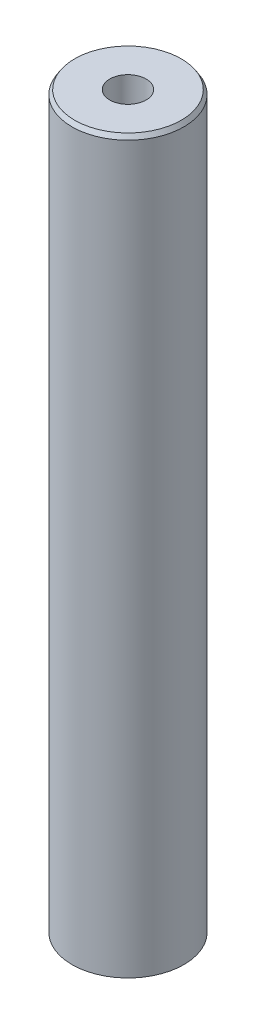
SolidWorks part; units mm, degrees
ref_plane "Front Plane" through (0, 0, 0) normal (0, 0, 1) x (1, 0, 0)
ref_plane "Top Plane" through (0, 0, 0) normal (0, 1, 0) x (1, 0, 0)
ref_plane "Right Plane" through (0, 0, 0) normal (1, 0, 0) x (0, 0, -1)
sketch "Sketch1" plane through (0, 0, 0) normal (0, 1, 0) x (1, 0, 0)
  circle A0 centre (0, 0) radius 35
  dimension "SHAFT_OD" = 70
extrude "Boss-Extrude1" add sketch "Sketch1" along normal blind 457.9796
sketch "Sketch2" plane through (0, 0, 0) normal (0, 1, 0) x (1, 0, 0)
  circle A0 centre (0, 0) radius 11.3816
  dimension "BORE_D" = 22.7633
extrude "Cut-Extrude1" cut sketch "Sketch2" along normal through all
chamfer "Chamfer1" distance 2.7229 angle 31.839 2 edges at (0, 457.9796, 35) (0, 0, 35) first distance on face at (0, 457.9796, 35) first distance on face at (0, 0, 11.3816)
